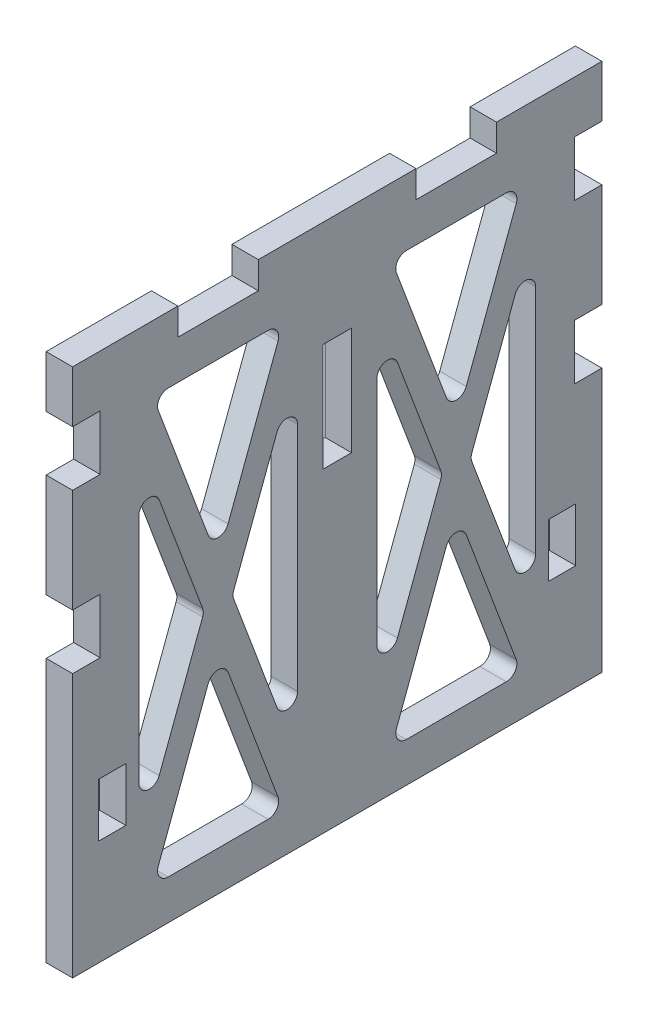
SolidWorks part; units mm, degrees
ref_plane "Front Plane" through (0, 0, 0) normal (0, 0, 1) x (1, 0, 0)
ref_plane "Top Plane" through (0, 0, 0) normal (0, 1, 0) x (1, 0, 0)
ref_plane "Right Plane" through (0, 0, 0) normal (1, 0, 0) x (0, 0, -1)
sketch "Sketch4" plane through (0, 0, 0) normal (1, 0, 0) x (0, 0, -1)
  line L0 (-3.175, 0) -> (-63.5, 0)
  line L3 (-3.175, 0) -> (3.175, 0) construction
  line L5 (3.175, 0) -> (63.5, 0)
  line L6 (63.5, 0) -> (63.5, 32.004)
  line L7 (63.5, 127) -> (38.227, 127)
  line L8 (-63.5, 127) -> (-63.5, 114.554)
  line L9 (0, 0) -> (0, 177.7936) construction
  line L10 (-3.429, 101.6) -> (3.429, 101.6)
  line L11 (-3.175, 101.346) -> (3.175, 101.346) construction
  line L12 (-3.175, 101.346) -> (-3.175, 75.946) construction
  line L13 (-3.175, 75.946) -> (3.175, 75.946) construction
  line L14 (3.175, 101.346) -> (3.175, 75.946) construction
  line L15 (3.429, 101.6) -> (3.429, 75.692)
  line L16 (-3.429, 75.692) -> (3.429, 75.692)
  line L17 (-3.429, 101.6) -> (-3.429, 75.692)
  line L18 (-63.5, 63.5) -> (-57.15, 63.5) construction
  line L19 (-57.15, 63.5) -> (-57.15, 76.2) construction
  line L20 (-57.15, 76.2) -> (-63.5, 76.2) construction
  line L21 (-63.5, 101.6) -> (-57.15, 101.6) construction
  line L22 (-57.15, 101.6) -> (-57.15, 114.3) construction
  line L23 (-57.15, 114.3) -> (-63.5, 114.3) construction
  line L24 (-63.5, 101.346) -> (-63.5, 76.454)
  line L25 (-63.5, 63.246) -> (-63.5, 38.354)
  line L32 (63.5, 114.554) -> (63.5, 127)
  line L34 (-63.5, 101.346) -> (-56.896, 101.346)
  line L35 (-56.896, 101.346) -> (-56.896, 114.554)
  line L36 (-56.896, 114.554) -> (-63.5, 114.554)
  line L37 (-63.5, 63.246) -> (-56.896, 63.246)
  line L38 (-56.896, 63.246) -> (-56.896, 76.454)
  line L39 (-56.896, 76.454) -> (-63.5, 76.454)
  line L40 (57.15, 114.3) -> (63.5, 114.3) construction
  line L41 (57.15, 101.6) -> (57.15, 114.3) construction
  line L42 (63.5, 101.6) -> (57.15, 101.6) construction
  line L43 (57.15, 76.2) -> (63.5, 76.2) construction
  line L44 (57.15, 63.5) -> (57.15, 76.2) construction
  line L45 (63.5, 63.5) -> (57.15, 63.5) construction
  line L46 (56.896, 76.454) -> (63.5, 76.454)
  line L47 (56.896, 63.246) -> (56.896, 76.454)
  line L48 (63.5, 63.246) -> (56.896, 63.246)
  line L49 (56.896, 114.554) -> (63.5, 114.554)
  line L50 (56.896, 101.346) -> (56.896, 114.554)
  line L51 (63.5, 101.346) -> (56.896, 101.346)
  line L52 (63.5, 101.346) -> (63.5, 76.454)
  line L53 (-18.923, 127) -> (-18.923, 120.523)
  line L59 (-19.05, 127) -> (-19.05, 120.65) construction
  line L60 (-19.05, 120.65) -> (-38.1, 120.65) construction
  line L61 (-38.1, 127) -> (-38.1, 120.65) construction
  line L62 (-18.923, 120.523) -> (-38.227, 120.523)
  line L63 (-38.227, 127) -> (-38.227, 120.523)
  line L64 (38.227, 127) -> (38.227, 120.523)
  line L65 (18.923, 120.523) -> (38.227, 120.523)
  line L66 (18.923, 127) -> (18.923, 120.523)
  line L67 (18.923, 127) -> (-18.923, 127)
  line L68 (-38.227, 127) -> (-63.5, 127)
  line L69 (63.5, 44.704) -> (63.5, 32.004)
  line L70 (50.8, 38.1) -> (50.8, 25.4) construction
  line L71 (57.15, 25.4) -> (50.8, 25.4) construction
  line L72 (57.15, 38.1) -> (57.15, 25.4) construction
  line L73 (-57.2262, 38.1762) -> (-50.7238, 38.1762)
  line L74 (-57.15, 38.1) -> (-50.8, 38.1) construction
  line L75 (-57.15, 38.1) -> (-57.15, 25.4) construction
  line L76 (0, 32.258) -> (6.35, 32.258) construction
  line L77 (57.15, 38.1) -> (50.8, 38.1) construction
  line L78 (57.2262, 38.1762) -> (57.2262, 25.3238)
  line L79 (57.2262, 25.3238) -> (50.7238, 25.3238)
  line L80 (-57.15, 25.4) -> (-50.8, 25.4) construction
  line L81 (-50.8, 38.1) -> (-50.8, 25.4) construction
  line L82 (-50.7238, 38.1762) -> (-50.7238, 25.3238)
  line L83 (-0.254, 32.512) -> (6.604, 32.512)
  line L84 (-63.5, 25.654) -> (-63.5, 0)
  line L85 (63.5, 44.704) -> (63.5, 63.246)
  line L86 (-63.5, 38.354) -> (-63.5, 25.654)
  line L87 (-57.2262, 25.3238) -> (-50.7238, 25.3238)
  line L88 (-57.2262, 38.1762) -> (-57.2262, 25.3238)
  line L89 (50.7238, 38.1762) -> (50.7238, 25.3238)
  line L90 (57.2262, 38.1762) -> (50.7238, 38.1762)
  line L91 (-3.175, 0) -> (3.175, 0)
  point P0 (0, 0)
  dimension "D3" = 60.325
  dimension "D4" = 127
  dimension "D5" = 6.35
  dimension "D6" = 25.4
  dimension "D8" = 25.4
  dimension "D9" = 12.7
  dimension "D10" = 12.7
  dimension "D11" = 6.35
  dimension "D12" = 25.4
  dimension "D15" = 25.4
  dimension "D16" = 19.05
  dimension "D17" = 6.35
  dimension "D19" = 6.35
  dimension "D20" = 12.7
  dimension "D21" = 25.4
  dimension "D22" = 6.35
  dimension "D24" = 127
  dimension "D7" = 0.254
  dimension "D13" = 0.254
  dimension "D14" = 0.254
  dimension "D18" = 0.127
  dimension "D23" = 0.0762
extrude "Boss-Extrude1" add sketch "Sketch4" along normal blind 6.35 contours L85 L48 L47 L46 L52 L51 L50 L49 L32 L7 L64 L65 L66 L67 L53 L62 L63 L68 L8 L36 L35 L34 L24 L39 L38 L37 L25 L73 L84 L0 L5 L6 L78 L17 L10 L15 L16 region at (0, 61.9793, 0)
sketch "Sketch5" plane through (6.35, 0, 0) normal (1, 0, 0) x (0, 0, -1)
  line L1 (-47.625, 111.125) -> (47.625, 111.125)
  line L2 (-47.625, 111.125) -> (-47.625, 9.525)
  line L3 (-47.625, 9.525) -> (47.625, 9.525)
  line L4 (47.625, 111.125) -> (47.625, 9.525)
  line L8 (0, 111.125) -> (0, 9.525) construction
  line L10 (-9.525, 111.125) -> (-9.525, 9.525)
  line L12 (9.525, 111.125) -> (9.525, 9.525)
  line L13 (9.525, 9.525) -> (47.625, 111.125) construction
  line L14 (6.5522, 10.6398) -> (44.6522, 112.2398)
  line L15 (12.4978, 8.4102) -> (50.5978, 110.0102)
  line L16 (47.625, 9.525) -> (9.525, 111.125) construction
  line L17 (44.6522, 8.4102) -> (6.5522, 110.0102)
  line L18 (50.5978, 10.6398) -> (12.4978, 112.2398)
  line L19 (-9.525, 9.525) -> (-47.625, 111.125) construction
  line L20 (-6.5522, 10.6398) -> (-44.6522, 112.2398)
  line L21 (-12.4978, 8.4102) -> (-50.5978, 110.0102)
  line L22 (-47.625, 9.525) -> (-9.525, 111.125) construction
  line L23 (-44.6522, 8.4102) -> (-6.5522, 110.0102)
  line L24 (-50.5978, 10.6398) -> (-12.4978, 112.2398)
  line L25 (63.5, 0) -> (63.5, 63.246) construction
  line L26 (63.5, 127) -> (38.227, 127) construction
  line L27 (-63.5, 63.246) -> (-63.5, 0) construction
  line L28 (63.5, 0) -> (-63.5, 0) construction
  arc A0 (6.5522, 10.6398) -> (12.4978, 8.4102) centre (9.525, 9.525) ccw
  arc A1 (50.5978, 110.0102) -> (44.6522, 112.2398) centre (47.625, 111.125) ccw
  arc A2 (44.6522, 8.4102) -> (50.5978, 10.6398) centre (47.625, 9.525) ccw
  arc A3 (12.4978, 112.2398) -> (6.5522, 110.0102) centre (9.525, 111.125) ccw
  arc A4 (-6.5522, 10.6398) -> (-12.4978, 8.4102) centre (-9.525, 9.525) cw
  arc A5 (-50.5978, 110.0102) -> (-44.6522, 112.2398) centre (-47.625, 111.125) cw
  arc A6 (-44.6522, 8.4102) -> (-50.5978, 10.6398) centre (-47.625, 9.525) cw
  arc A7 (-12.4978, 112.2398) -> (-6.5522, 110.0102) centre (-9.525, 111.125) cw
  point P18 (28.575, 60.325)
  point P23 (28.575, 60.325)
  point P28 (-28.575, 60.325)
  point P33 (-28.575, 60.325)
  dimension "D6" = 3.175
  dimension "D1" = 15.875
  dimension "D2" = 15.875
  dimension "D3" = 15.875
  dimension "D4" = 9.525
  dimension "D5" = 19.05
extrude "Cut-Extrude1" cut sketch "Sketch5" against normal through all contours L2 L24 L21 | L20 L24 L1 | L23 L3 L21 | L14 L17 L12 | L18 L14 L1 | L18 L4 L15 | L3 L17 L15 | L23 L20 L10 region at (6.35, 97.2058, 28.575) region at (6.35, 60.325, 42.4053) region at (6.35, 60.325, 14.7447) region at (6.35, 23.4442, 28.575) region at (6.35, 97.2058, -28.575) region at (6.35, 60.325, -14.7447) region at (6.35, 60.325, -42.4053) region at (6.35, 23.4442, -28.575)
fillet "Fillet1" radius 2.54 24 edges at (3.175, 51.2826, 28.575) (3.175, 9.525, 12.9159) (3.175, 9.525, 44.2341) (3.175, 102.0826, 9.525) (3.175, 18.5674, 9.525) (3.175, 60.325, 25.1841) (3.175, 51.2826, -28.575) (3.175, 9.525, -44.2341) (3.175, 9.525, -12.9159) (3.175, 60.325, -31.9659) (3.175, 102.0826, -47.625) (3.175, 18.5674, -47.625) (3.175, 60.325, 31.9659) (3.175, 18.5674, 47.625) (3.175, 102.0826, 47.625) (3.175, 111.125, -12.9159) (3.175, 111.125, -44.2341) (3.175, 69.3674, -28.575) (3.175, 111.125, 12.9159) (3.175, 69.3674, 28.575) (3.175, 102.0826, -9.525) (3.175, 60.325, -25.1841) (3.175, 18.5674, -9.525) (3.175, 111.125, 44.2341)
fillet "Fillet2" [suppressed] radius 2.54
